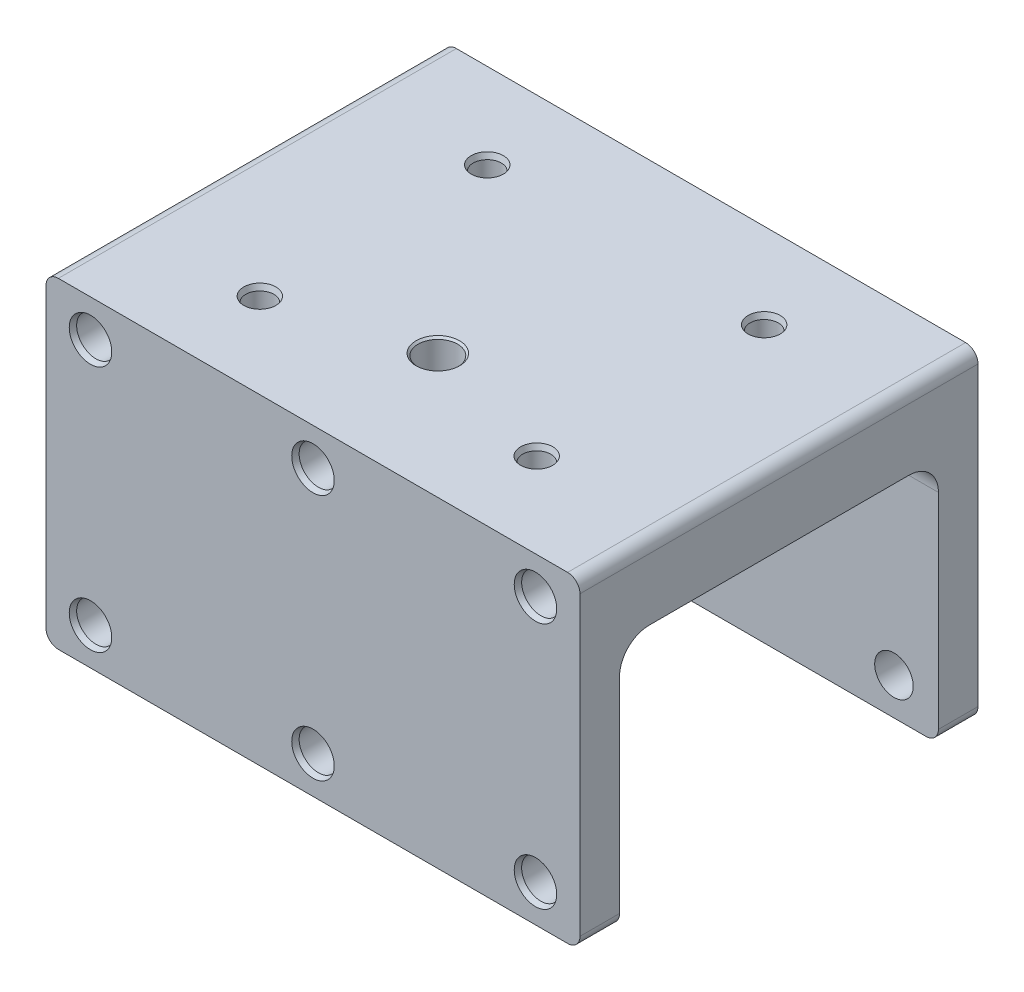
SolidWorks part; units mm, degrees
ref_plane "Front" through (0, 0, 0) normal (0, 0, 1) x (1, 0, 0)
ref_plane "Top" through (0, 0, 0) normal (0, 1, 0) x (1, 0, 0)
ref_plane "Right" through (0, 0, 0) normal (1, 0, 0) x (0, 0, -1)
sketch "Sketch1" plane through (0, 0, 0) normal (0, 1, 0) x (1, 0, 0)
  line L1 (0, 0) -> (108, 0)
  line L2 (0, 0) -> (0, 80.5)
  line L3 (0, 80.5) -> (108, 80.5)
  line L4 (108, 0) -> (108, 80.5)
  dimension "D1" = 80.5
  dimension "D2" = 108
extrude "Boss-Extrude1" add sketch "Sketch1" along normal blind 15
sketch "Sketch2" plane through (0, 0, 0) normal (0, 0, 1) x (1, 0, 0)
  line L0 (54, 15) -> (54, 0) construction
  line L1 (0, 15) -> (108, 15) construction
  line L2 (0, 0) -> (108, 0) construction
  line L3 (9, 7.5) -> (99, 7.5) construction
  circle A0 centre (9, 7.5) radius 3.9
  circle A1 centre (99, 7.5) radius 3.9
  circle A2 centre (54, 7.5) radius 3.9
  point P9 (54, 7.5)
  dimension "D2" = 7.8
  dimension "D3" = 7.8
  dimension "D1" = 90
extrude "Cut-Extrude1" cut sketch "Sketch2" against normal blind 7
sketch "Sketch3" plane through (0, 0, 0) normal (0, 0, 1) x (1, 0, 0)
  line L0 (108, 15) -> (108, 0) construction
  line L1 (0, 0) -> (108, 0)
  line L2 (0, 0) -> (0, -50)
  line L3 (0, -50) -> (108, -50)
  line L4 (108, 0) -> (108, -50)
  line L5 (0, -42.5) -> (108, -42.5) construction
  line L6 (0, 15) -> (108, 15) construction
  line L7 (0, 15) -> (108, 15) construction
  line L8 (9, 7.5) -> (9, -42.5) construction
  line L9 (99, 7.5) -> (99, -42.5) construction
  circle A0 centre (99, 7.5) radius 3.9 construction
  circle A1 centre (99, 7.5) radius 3.9 construction
  circle A2 centre (99, 7.5) radius 3.9 construction
  circle A3 centre (99, -42.5) radius 3.9
  circle A4 centre (54, -42.5) radius 3.9
  circle A5 centre (9, -42.5) radius 3.9
  dimension "D1" = 50
  dimension "D2" = 7.5
  dimension "D3" = 7.5
extrude "Boss-Extrude2" add sketch "Sketch3" against normal blind 8
ref_plane "Plane1" through (0, 0, -40.25) normal (0, 0, 1) x (1, 0, 0)
mirror "Mirror1" about plane through (0, 0, -40.25) normal (0, 0, 1) of "Boss-Extrude2", "Cut-Extrude1"
chamfer "Chamfer1" distance 0.4 angle 70 12 edges at (102.9, 7.5, -80.5) (12.9, 7.5, -80.5) (102.9, 7.5, 0) (12.9, 7.5, 0) (57.9, 7.5, -80.5) (57.9, 7.5, 0) (12.9, -42.5, -80.5) (57.9, -42.5, -80.5) (102.9, -42.5, -80.5) (57.9, -42.5, 0) (12.9, -42.5, 0) (102.9, -42.5, 0) first distance on face at (12.9, 7.5, -80.5) first distance on face at (12.9, 7.5, 0)
fillet "Fillet1" radius 2.5 6 edges at (0, 15, -40.25) (108, 15, -40.25) (0, -50, -76.5) (0, -50, -4) (108, -50, -76.5) (108, -50, -4)
fillet "Fillet2" radius 6 2 edges at (54, 0, -72.5) (54, 0, -8)
sketch "Sketch4" plane through (0, 15, 0) normal (0, 1, 0) x (1, 0, 0)
  line L0 (54, 0) -> (54, 80.5) construction
  line L1 (2.5, 0) -> (105.5, 0) construction
  line L2 (105.5, 80.5) -> (2.5, 80.5) construction
  line L4 (26, 63.25) -> (82, 63.25) construction
  line L5 (26, 63.25) -> (26, 17.25) construction
  line L6 (26, 17.25) -> (82, 17.25) construction
  line L7 (82, 63.25) -> (82, 17.25) construction
  line L8 (26, 63.25) -> (82, 17.25) construction
  line L9 (26, 17.25) -> (82, 63.25) construction
  circle A0 centre (82, 17.25) radius 2.85
  circle A1 centre (26, 17.25) radius 2.85
  circle A2 centre (26, 63.25) radius 2.85
  circle A3 centre (82, 63.25) radius 2.85
  point P6 (54, 40.25)
  dimension "D4" = 5.7
  dimension "D1" = 46
  dimension "D2" = 56
  dimension "D3" = 17.25
extrude "Cut-Extrude2" cut sketch "Sketch4" against normal blind 11
chamfer "Chamfer2" distance 0.4 angle 70 4 edges at (26, 15, -60.4) (82, 15, -60.4) (26, 15, -14.4) (82, 15, -14.4) first distance on face at (82, 15, -60.4)
sketch "Sketch5" plane through (0, 15, 0) normal (0, 1, 0) x (1, 0, 0)
  line L0 (82, 17.25) -> (26, 17.25) construction
  line L1 (54, 17.25) -> (54, 25.25) construction
  circle A0 centre (54, 25.25) radius 4
  dimension "D2" = 8
  dimension "D1" = 8
extrude "Cut-Extrude3" cut sketch "Sketch5" against normal through all
chamfer "Chamfer3" distance 0.4 angle 45 1 edges at (54, 15, -21.25)
equation "\"Length\"= 108"
equation "\"D2@Sketch1\"=\"Length\""
equation "\"Hole_Spacing\"= 90"
equation "\"D1@Sketch2\"=\"Hole_Spacing\""
equation "\"D3@Sketch3\"=\"D2@Sketch3\""
